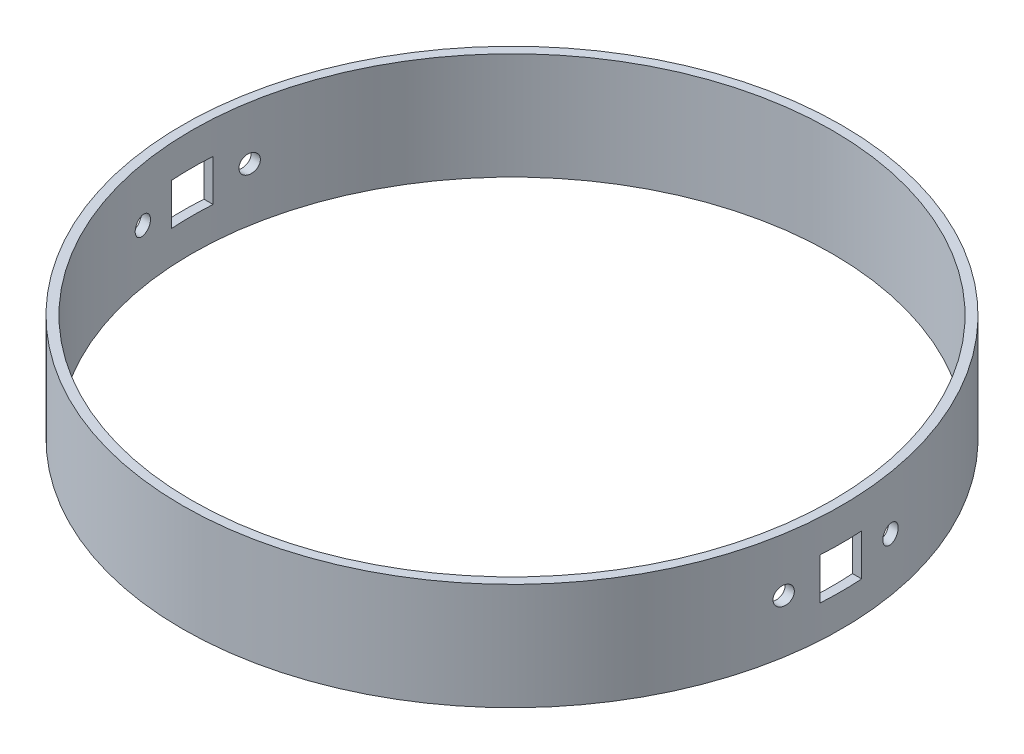
SolidWorks part; units mm, degrees
material "A-Glass Fiber"
ref_plane "Front Plane" through (0, 0, 0) normal (0, 0, 1) x (1, 0, 0)
ref_plane "Top Plane" through (0, 0, 0) normal (0, 1, 0) x (1, 0, 0)
ref_plane "Right Plane" through (0, 0, 0) normal (1, 0, 0) x (0, 0, -1)
sketch "Sketch1" plane through (0, 0, 0) normal (0, 1, 0) x (1, 0, 0)
  circle A0 centre (0, 0) radius 78.359
  circle A1 centre (0, 0) radius 76.1746
  dimension "D1" = 156.718
  dimension "D2" = 152.3492
extrude "Boss-Extrude1" add sketch "Sketch1" along normal blind 25.4
sketch "Sketch2" plane through (0, 0, 0) normal (1, 0, 0) x (0, 0, -1)
  line L0 (-78.359, 0) -> (78.359, 0) construction
  line L7 (0, 12.7) -> (0, 14.52) construction
  line L12 (4.953, 7.747) -> (-4.953, 7.747)
  line L13 (0, 25.4) -> (0, 0) construction
  line L14 (76.1746, 25.4) -> (-76.1746, 25.4) construction
  line L15 (-78.359, 0) -> (78.359, 0)
  line L16 (76.1746, 25.4) -> (-76.1746, 25.4)
  line L17 (-28.7231, 12.7) -> (26.1298, 12.7) construction
  line L25 (4.953, 7.747) -> (4.953, 17.653)
  line L26 (4.953, 17.653) -> (-4.953, 17.653)
  line L27 (-4.953, 7.747) -> (-4.953, 17.653)
  line L28 (4.953, 7.747) -> (-4.953, 17.653) construction
  line L29 (4.953, 17.653) -> (-4.953, 7.747) construction
  circle A0 centre (-12.7, 12.7) radius 2.1831
  circle A1 centre (12.7, 12.7) radius 2.1831
  point P0 (0, 9.85)
  point P1 (0, 0)
  point P14 (0, 3.175)
  point P27 (0, 12.7)
  dimension "D4" = 9.906
  dimension "D8" = 4.3663
  dimension "D1" = 12.7
  dimension "D5" = 9.906
extrude "Cut-Extrude1" cut sketch "Sketch2" along normal through all both and the other way through all contours L25 L12 L27 L26 | A1 | A0
ref_plane "Plane1" through (0, 0, 0) normal (0.9973, 0, 0.0728) x (0, -1, 0)
sketch "Sketch5" plane through (0, 0, 0) normal (0.9973, 0, 0.0728) x (0, -1, 0)
  line L0 (-13.35, 0.7076) -> (-13.35, 10.681) construction
  circle A0 centre (-20.335, 0) radius 2.75
  dimension "D1" = 5.5
  dimension "D2" = 6.985
extrude "Cut-Extrude2" [suppressed] cut sketch "Sketch5" along normal through all
ref_plane "Plane2" through (0, 12.7, 0) normal (0, 1, 0) x (1, 0, 0)
pattern_circular "CirPattern1" [suppressed] count 2 every 8.407 of bodies 104
mirror "Mirror2" about plane through (0, 0, 0) normal (1, 0, 0) of "Cut-Extrude1", "CirPattern1", "Boss-Extrude1" second plane through (0, 12.7, 0) second plane normal (0, 1, 0)
sketch "Sketch8" plane through (0, 0, 0) normal (1, 0, 0) x (0, 0, -1)
  line L0 (0, 25.4) -> (0, 0) construction
  line L1 (5, 15.225) -> (-5, 15.225)
  line L2 (5, 15.225) -> (5, 22.225)
  line L3 (5, 22.225) -> (-5, 22.225)
  line L4 (-5, 15.225) -> (-5, 22.225)
  line L5 (5, 15.225) -> (-5, 22.225) construction
  line L6 (5, 22.225) -> (-5, 15.225) construction
  line L8 (78.359, 25.4) -> (-78.359, 25.4) construction
  circle A0 centre (0, 6.335) radius 2.75
  point P0 (0, 18.725)
  dimension "D4" = 5.5
  dimension "D1" = 10
  dimension "D2" = 7
  dimension "D3" = 3.175
  dimension "D5" = 8.89
extrude "Cut-Extrude3" [suppressed] cut sketch "Sketch8" against normal through all
sketch "Sketch9" [suppressed] plane through (0, 0, 0) normal (0.9973, 0, 0.0728) x (0, -1, 0)
  line L0 (-15.225, -10.6344) -> (-15.225, -10.681) construction
  line L1 (-25.4, 0) -> (0, 0) construction
  circle A0 centre (-11.415, 0) radius 2.75
  dimension "D1" = 5.5
  dimension "D2" = 3.81
extrude "Cut-Extrude4" [suppressed] cut sketch "Sketch9" against normal through all
pattern_circular "CirPattern2" [suppressed] count 2 every 8.41 of bodies 109
equation "\"Mid_Tube_Length\"= 1in"
equation "\"Bodytube_OD\" = 6.17in"
equation "\"Bodytube_ID\" = 5.998in"
equation "\"D1@Sketch1\"=\"Bodytube_OD\""
equation "\"D2@Sketch1\"= \"Bodytube_ID\""
equation "\"Camera_Cutout_Width\"=10mm"
equation "\"Camera_Cutout_Height\"=7mm"
equation "\"Fwd_Tube_Length\" = 40in"
equation "\"BKHD_Screw_Diam\"= 3.5mm"
equation "\"Fwd_BKHD_From_Top\" = 18in"
equation "\"Shear_Screw_Diameter\" = 0.086in"
equation "\"Shear_Screw_Coupler_Location\" = 4.5in"
equation "\"Motor_OD\" = 4in"
equation "\"Mid_Coupler_Length\" = 13in"
equation "\"Aft_Section_Length\"= 39in"
equation "\"AB_Coupler_OD_Length\"= 1in"
equation "\"AB_Coupling_Section_Length\"= 0.375in"
equation "\"AB_Coupler_Length\"= \"AB_Coupler_OD_Length\" + \"AB_Coupling_Section_Length\" * 2"
equation "\"Cutout_Angle\" = 80"
equation "\"AB_Paddle_Height\" = 0.375in"
equation "\"AB_Coupler_Num_Screws\"= 4"
equation "\"AB_BKHD_Thickness\" = 0.375in"
equation "\"AB_Mount_From_Bottom\" = 23.175in"
equation "\"Num_Cutouts\" = 3"
equation "\"AB_Coupler_OD\"= 6.17in"
equation "\"AB_Coupler_ID\"= 5.75in"
equation "\"AB_Coupler_Surface_Diameter\"= 5.998in"
equation "\"AB_Coupling_Screw_Diameter\"= 0.15748in"
equation "\"AB_Central_Bushing_Length\" = .4724in"
equation "\"Lead_Screw_Dist\" = 3.4in"
equation "\"Lead_Screw_Diam\" = 0.386in"
equation "\"Lead_Screw_Length\" = (\"Mid_Coupler_Length\" + 2*0.375in + 2*0.5in)"
equation "\"Paddle_Pin_Offset\" = .25in"
equation "\"Paddle_Pin_Radius\" = 2.25in"
equation "\"SS_Paddle_Pin_Radius\" = 2.25*0.66in"
equation "\"Paddle_Gear_OD\" = 3.2in"
equation "\"Drive_Gear_OD\" = 1.7in"
equation "\"Fin_Thickness\"= .118in"
equation "\"Guiderail_Cutout_Diameter\"= 1.5in"
equation "\"DB9_Hole_Dist\" = 25mm"
equation "\"DB9_Relief_Width\" = 0.47in"
equation "\"DB9_Relief_Hole_Offset\" = 0.09in"
equation "\"Airbrakes_Wire_Hole_Dia\" = .25in"
equation "\"Airbrakes_Wire_Hole_Dist\" = 1.1in"
equation "\"Servo_Gear_Offset\" = 0.5in"
equation "\"FWD_Shear_Screw_Dist\" = 1.5in"
equation "\"Camera_Screw_Dia\" = 0.216535"
equation "\"D1@Sketch5\"=\"Camera_Screw_Dia\""
equation "\"Camera_Hole_Angle\" = atn ( 2 / 3 * tan ( 12.5deg ) )"
equation "\"D2@CirPattern1\"=\"Camera_Hole_Angle\""
equation "\"D4@Sketch8\"=\"Camera_Screw_Dia\""
equation "\"D1@Sketch9\"=\"Camera_Screw_Dia\""
